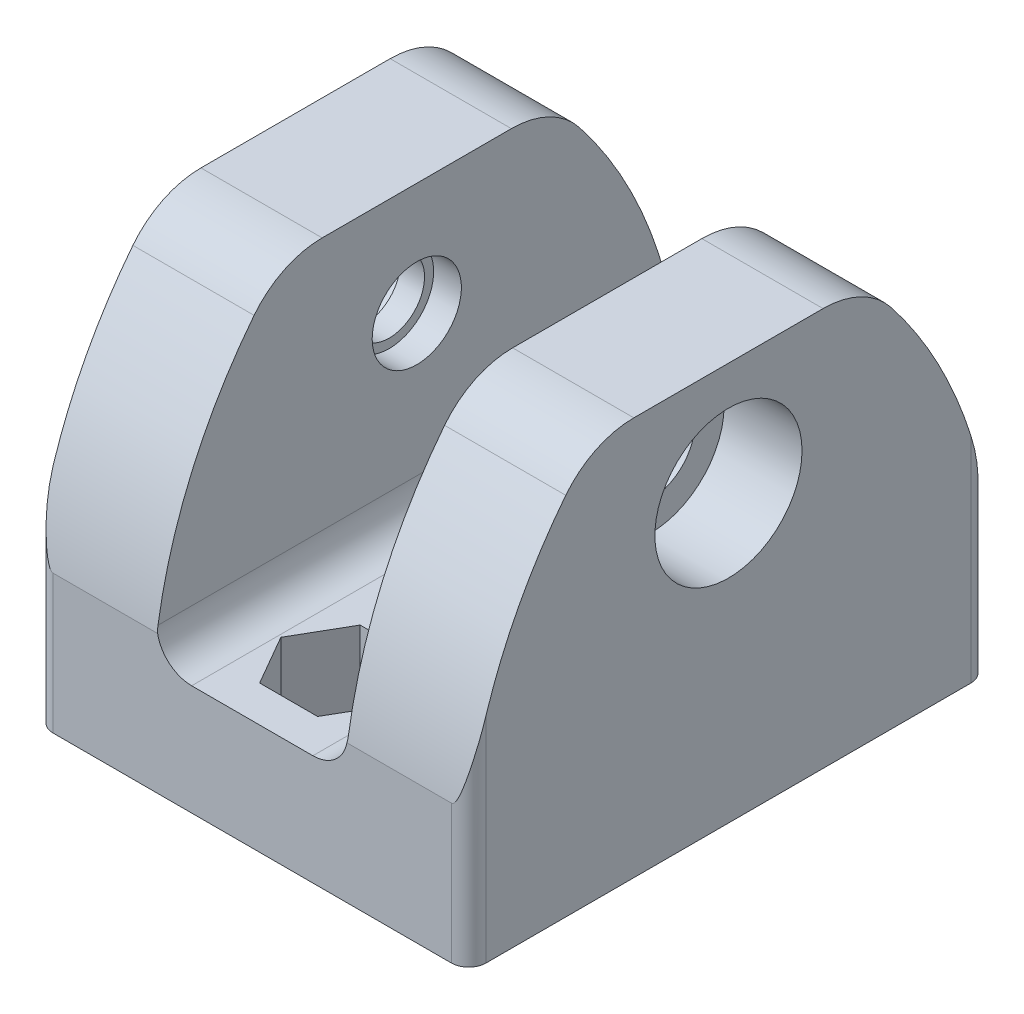
SolidWorks part; units mm, degrees
ref_plane "Alzado" through (0, 0, 0) normal (0, 0, 1) x (1, 0, 0)
ref_plane "Planta" through (0, 0, 0) normal (0, 1, 0) x (1, 0, 0)
ref_plane "Vista lateral" through (0, 0, 0) normal (1, 0, 0) x (0, 0, -1)
sketch "Croquis1" plane through (0, 0, 0) normal (0, 1, 0) x (1, 0, 0)
  line L0 (12.5, 30) -> (12.5, 0) construction
  line L1 (0, 0) -> (25, 0)
  line L2 (0, 0) -> (0, 30)
  line L3 (0, 30) -> (25, 30)
  line L4 (25, 0) -> (25, 30)
  circle A0 centre (12.5, 25) radius 1.55
  circle A1 centre (12.5, 5) radius 1.55
  dimension "D3" = 20
  dimension "D4" = 3.1
  dimension "D1" = 25
  dimension "D2" = 30
  dimension "D5" = 5
extrude "Saliente-Extruir1" add sketch "Croquis1" along normal blind 23
sketch "Croquis2" plane through (0, 0, -30) normal (0, 0, -1) x (-1, 0, 0)
  line L0 (-25, 23) -> (0, 23) construction
  line L1 (-8, 23) -> (-17, 23)
  line L2 (-8, 23) -> (-8, 6.3673)
  line L3 (-8, 6.3673) -> (-17, 6.3673)
  line L4 (-17, 23) -> (-17, 6.3673)
  line L5 (0, 23) -> (0, 0) construction
  dimension "D1" = 9
  dimension "D2" = 8
extrude "Cortar-Extruir1" cut sketch "Croquis2" against normal up to surface (30 mm away) up to face at (12.5, 11.5, 0)
sketch "Croquis3" plane through (0, 0, 0) normal (-1, 0, 0) x (0, 0, 1)
  line L0 (-15, 0) -> (-15, 23) construction
  line L1 (-30, 0) -> (0, 0) construction
  line L2 (-30, 23) -> (0, 23) construction
  circle A0 centre (-15, 16.5) radius 2.575
  dimension "D1" = 5.15
  dimension "D2" = 6.5
extrude "Cortar-Extruir2" cut sketch "Croquis3" against normal up to surface (25 mm away) up to face at (25, 11.5, -15)
sketch "Croquis4" plane through (0, 0, 0) normal (-1, 0, 0) x (0, 0, 1)
  line L1 (-14.9518, 20.5412) -> (-18.4757, 18.5623)
  line L2 (-18.4757, 18.5623) -> (-18.5238, 14.5212)
  line L3 (-18.5238, 14.5212) -> (-15.0482, 12.4588)
  line L4 (-15.0482, 12.4588) -> (-11.5243, 14.4377)
  line L5 (-11.5243, 14.4377) -> (-11.4762, 18.4788)
  line L6 (-11.4762, 18.4788) -> (-14.9518, 20.5412)
  circle A0 centre (-15, 16.5) radius 3.5 construction
  dimension "D1" = 7
extrude "Cortar-Extruir3" cut sketch "Croquis4" against normal blind 2.5
sketch "Croquis5" plane through (25, 0, 0) normal (1, 0, 0) x (0, 0, -1)
  circle A0 centre (15, 16.5) radius 4.25
  dimension "D1" = 8.5
extrude "Cortar-Extruir4" cut sketch "Croquis5" against normal blind 4.5
sketch "Croquis6" plane through (0, 6.3673, 0) normal (0, 1, 0) x (1, 0, 0)
  line L1 (15.8486, 25) -> (14.1743, 27.9)
  line L2 (14.1743, 27.9) -> (10.8257, 27.9)
  line L3 (10.8257, 27.9) -> (9.1514, 25)
  line L4 (9.1514, 25) -> (10.8257, 22.1)
  line L5 (10.8257, 22.1) -> (14.1743, 22.1)
  line L6 (14.1743, 22.1) -> (15.8486, 25)
  line L7 (15.8486, 5) -> (14.1743, 7.9)
  line L8 (14.1743, 7.9) -> (10.8257, 7.9)
  line L9 (10.8257, 7.9) -> (9.1514, 5)
  line L10 (9.1514, 5) -> (10.8257, 2.1)
  line L11 (10.8257, 2.1) -> (14.1743, 2.1)
  line L12 (14.1743, 2.1) -> (15.8486, 5)
  circle A0 centre (12.5, 25) radius 2.9 construction
  circle A1 centre (12.5, 5) radius 2.9 construction
  dimension "D1" = 5.8
  dimension "D2" = 5.8
extrude "Cortar-Extruir5" cut sketch "Croquis6" against normal blind 4.5
sketch "Croquis7" plane through (0, 0, 0) normal (-1, 0, 0) x (0, 0, 1)
  line L0 (-15, 0) -> (-15, 23) construction
  line L1 (-30, 0) -> (0, 0) construction
  line L2 (-30, 23) -> (0, 23) construction
  line L3 (-30, 23) -> (-30, 8)
  line L4 (-30, 23) -> (-30, 0) construction
  line L5 (-30, 23) -> (-22.746, 23)
  line L6 (0, 23) -> (-7.254, 23)
  line L7 (0, 23) -> (0, 8)
  circle A0 centre (-15, 17.5) radius 9.5
  arc A1 (-30, 8) -> (-22.746, 23) centre (-2.7727, 4.0869) cw
  arc A2 (0, 8) -> (-7.254, 23) centre (-27.2273, 4.0869) ccw
  line M8 (0, 0) -> (0, 23)
  line M9 (0, 23) -> (-30, 23)
  line M10 (-30, 23) -> (-30, 0)
  dimension "D1" = 19
  dimension "D2" = 8
  dimension "D3" = 5.5
extrude "Cortar-Extruir6" cut sketch "Croquis7" against normal up to surface (25 mm away) contours A1 M10 M9 | A2 M8 M9 region at (0, 18.8202, -27.8499) region at (0, 18.8202, -2.1501) up to face at (25, 16.5, -19.25)
fillet "Redondeo3" radius 1 4 edges at (25, 4, 0) (0, 4, 0) (0, 4, -30) (25, 4, -30)
sketch "Croquis8" plane through (2.5, 0, 0) normal (-1, 0, 0) x (0, 0, 1)
  circle A0 centre (-15, 16.5) radius 2.575 construction
  circle A1 centre (-15, 16.5) radius 2.575
  circle A2 centre (-15, 16.5) radius 2.05
  dimension "D1" = 4.1
extrude "Saliente-Extruir2" add sketch "Croquis8" against normal blind 2.9
sketch "Croquis9" plane through (2.5, 0, 0) normal (-1, 0, 0) x (0, 0, 1)
  line L6 (-11.4762, 18.4788) -> (-14.9518, 20.5412)
  line L7 (-14.9518, 20.5412) -> (-18.4757, 18.5623)
  line L8 (-18.4757, 18.5623) -> (-18.5238, 14.5212)
  line L9 (-18.5238, 14.5212) -> (-15.0482, 12.4588)
  line L10 (-15.0482, 12.4588) -> (-11.5243, 14.4377)
  line L11 (-11.5243, 14.4377) -> (-11.4762, 18.4788)
  line L12 (-11.4762, 18.4788) -> (-14.9518, 20.5412)
  line L13 (-14.9518, 20.5412) -> (-18.4757, 18.5623)
  line L14 (-18.4757, 18.5623) -> (-18.5238, 14.5212)
  line L15 (-18.5238, 14.5212) -> (-15.0482, 12.4588)
  line L16 (-15.0482, 12.4588) -> (-11.5243, 14.4377)
  line L17 (-11.5243, 14.4377) -> (-11.4762, 18.4788)
  dimension "D1" = 0
extrude "Cortar-Extruir7" cut sketch "Croquis9" against normal blind 1.5
sketch "Croquis10" plane through (0, 23, 0) normal (0, 1, 0) x (1, 0, 0)
  line L0 (24, 30) -> (17, 30) construction
  line L1 (17, 0) -> (18, 0)
  line L2 (17, 0) -> (17, 30)
  line L3 (17, 30) -> (18, 30)
  line L4 (18, 0) -> (18, 30)
  line L5 (8, 30) -> (1, 30) construction
  line L6 (8, 0) -> (7, 0)
  line L7 (8, 0) -> (8, 30)
  line L8 (8, 30) -> (7, 30)
  line L9 (7, 0) -> (7, 30)
  dimension "D1" = 1
  dimension "D2" = 1
extrude "Cortar-Extruir8" cut sketch "Croquis10" against normal up to surface (16.6327 mm away) up to face at (12.5, 6.3673, -25)
fillet "Redondeo4" radius 5 4 edges at (21.5, 23, -22.746) (21.5, 23, -7.254) (3.5, 23, -7.254) (3.5, 23, -22.746)
fillet "Redondeo5" radius 2 2 edges at (7, 6.3673, -15) (18, 6.3673, -15)
